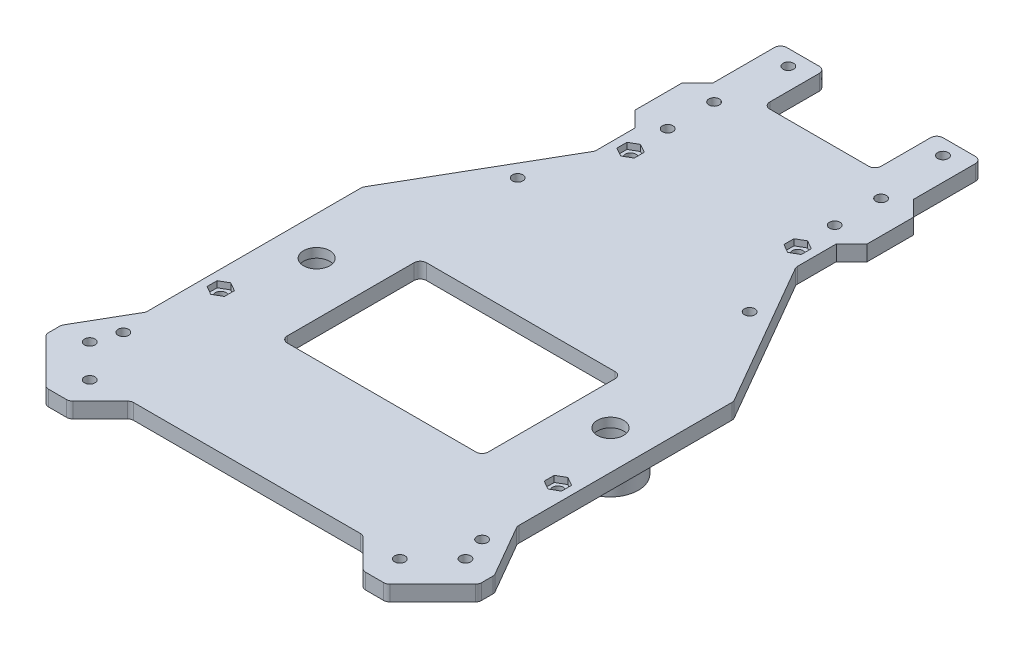
SolidWorks part; units mm, degrees
material "ABS PC"
ref_plane "Front Plane" through (0, 0, 0) normal (0, 0, 1) x (1, 0, 0)
ref_plane "Top Plane" through (0, 0, 0) normal (0, 1, 0) x (1, 0, 0)
ref_plane "Right Plane" through (0, 0, 0) normal (1, 0, 0) x (0, 0, -1)
sketch "Sketch1" plane through (0, 0, 0) normal (0, 1, 0) x (1, 0, 0)
  line L1 (70, -110) -> (-70, -110)
  line L2 (70, -110) -> (70, 110)
  line L3 (70, 110) -> (-70, 110)
  line L4 (-70, -110) -> (-70, 110)
  line L5 (70, -110) -> (-70, 110) construction
  line L6 (70, 110) -> (-70, -110) construction
  point P0 (0, 0)
  dimension "D1" = 220
  dimension "D2" = 140
extrude "Boss-Extrude1" add sketch "Sketch1" along normal blind 5
sketch "Sketch2" plane through (0, 5, 0) normal (0, 1, 0) x (1, 0, 0)
  line L0 (0, 110) -> (0, -110) construction
  line L1 (70, 110) -> (-70, 110) construction
  line L2 (-70, -110) -> (70, -110) construction
  line L4 (15.25, 80.25) -> (-15.25, 80.25) construction
  line L5 (15.25, 80.25) -> (15.25, 49.75) construction
  line L6 (15.25, 49.75) -> (-15.25, 49.75) construction
  line L7 (-15.25, 80.25) -> (-15.25, 49.75) construction
  line L8 (15.25, 80.25) -> (-15.25, 49.75) construction
  line L9 (15.25, 49.75) -> (-15.25, 80.25) construction
  point P6 (0, 65)
  dimension "D1" = 30.5
  dimension "D2" = 45
sketch "Sketch5" plane through (0, 5, 0) normal (0, 1, 0) x (1, 0, 0)
  line L0 (0, 110) -> (0, -110) construction
  line L1 (70, 110) -> (-70, 110) construction
  line L2 (-70, -110) -> (70, -110) construction
  line L4 (-24.5, -34) -> (24.5, -34) construction
  line L5 (-24.5, -34) -> (-24.5, 24) construction
  line L6 (-24.5, 24) -> (24.5, 24) construction
  line L7 (24.5, -34) -> (24.5, 24) construction
  line L8 (-24.5, -34) -> (24.5, 24) construction
  line L9 (-24.5, 24) -> (24.5, -34) construction
  point P6 (0, -5)
  dimension "D1" = 58
  dimension "D2" = 49
  dimension "D3" = 115
sketch "Sketch8" plane through (0, 5, 0) normal (0, 1, 0) x (1, 0, 0)
  line L0 (-70, 110) -> (-32.5, 110)
  line L1 (70, 110) -> (-70, 110) construction
  line L2 (-32.5, 110) -> (-32.5, 44.9519)
  line L3 (-32.5, 44.9519) -> (-70, -20)
  line L4 (-70, 110) -> (-70, -110) construction
  line L5 (-70, 110) -> (-70, -20)
  line L6 (0, 110) -> (0, -110) construction
  line L7 (-70, -110) -> (70, -110) construction
  line L8 (70, 110) -> (70, -20)
  line L9 (32.5, 44.9519) -> (70, -20)
  line L10 (32.5, 110) -> (32.5, 44.9519)
  line L11 (70, 110) -> (32.5, 110)
  dimension "D1" = 130
  dimension "D2" = 30
  dimension "D3" = 65
extrude "Cut-Extrude1" cut sketch "Sketch8" against normal blind 5
chamfer "Chamfer3" distance 15 angle 45 2 edges at (70, 2.5, 110) (-70, 2.5, 110)
sketch "Sketch10" plane through (0, 0, 0) normal (0, 1, 0) x (1, 0, 0)
  line L0 (0, 110) -> (0, -110) construction
  line L1 (32.5, 110) -> (-32.5, 110) construction
  line L2 (-55, -110) -> (55, -110) construction
  line L3 (-27, 78) -> (-27, 63) construction
  line L4 (-62.5, -102.5) -> (-55.4289, -95.4289) construction
  line L5 (-60.7322, -90.1256) -> (-50.1256, -100.7322) construction
  line L6 (-70, -95) -> (-55, -110) construction
  point P9 (27, 63)
  point P10 (27, 78)
  point P17 (50.1256, -100.7322)
  point P18 (60.7322, -90.1256)
  dimension "D1" = 15
  dimension "D2" = 27
  dimension "D3" = 32
  dimension "D4" = 15
  dimension "D5" = 10
sketch "Sketch15" plane through (0, 5, 0) normal (0, 1, 0) x (1, 0, 0)
  line L0 (0, 110) -> (0, -110) construction
  line L1 (32.5, 110) -> (-32.5, 110) construction
  line L2 (-55, -110) -> (55, -110) construction
  line L3 (25, 100) -> (-25, 100) construction
  line L4 (37.5, 25) -> (-37.5, 25) construction
  line L5 (58, -57) -> (-58, -57) construction
  point P9 (0, 100)
  point P13 (0, 25)
  point P15 (0, -57)
  dimension "D1" = 50
  dimension "D2" = 10
  dimension "D3" = 75
  dimension "D4" = 85
  dimension "D5" = 116
  dimension "D6" = 167
hole_wizard "CSK for M3 Flat Head Machine Screw3" positions "Sketch16" profile "Sketch17" countersink size "M3" standard "ANSI Metric"
sketch "Sketch16" plane through (0, 0, 0) normal (0, 1, 0) x (1, 0, 0)
  point P6 (37.5, 25)
  point P9 (-37.5, 25)
  point P12 (-25, 100)
  point P15 (25, 100)
sketch "Sketch17" plane through (37.5, 0, -25) normal (1, 0, 0) x (0, 0, -1)
  line L0 (0, 0) -> (0, 6.0215)
  line L1 (0, 6.0215) -> (1.7, 5)
  line L2 (1.7, 5) -> (1.7, 1.45)
  line L3 (1.7, 1.45) -> (3.15, 0)
  line L5 (3.15, 0) -> (0, 0)
  line L6 (-1.7, 1.45) -> (-3.15, 0) construction
  line L10 (0, 6.0215) -> (-1.7, 5) construction
  line L11 (0, -6.35) -> (0, 107.95) construction
  dimension "Hole Dia." = 3.4
  dimension "Hole Depth" = 5
  dimension "Near C'Sink Dia." = 6.3
  dimension "Near C'Sink Angle" = 90
  dimension "Drill Angle" = 118
sketch "Sketch18" plane through (0, 5, 0) normal (0, 1, 0) x (1, 0, 0)
  line L0 (32.5, 110) -> (-32.5, 110) construction
  line L1 (-46.4338, 114.6286) -> (34.8035, 114.6286)
  line L2 (-46.4338, 114.6286) -> (-46.4338, 105)
  line L3 (-46.4338, 105) -> (34.8035, 105)
  line L4 (34.8035, 114.6286) -> (34.8035, 105)
  dimension "D1" = 5
extrude "Cut-Extrude2" cut sketch "Sketch18" against normal blind 5
sketch "Sketch20" [suppressed] plane through (0, 5, 0) normal (0, 1, 0) x (1, 0, 0)
  line L0 (-36.4478, -76.4478) -> (-74.4101, -114.4101) construction
  line L1 (-27, 81.4641) -> (-30, 79.7321)
  line L2 (-30, 79.7321) -> (-30, 76.2679)
  line L3 (-30, 76.2679) -> (-27, 74.5359)
  line L4 (-27, 74.5359) -> (-24, 76.2679)
  line L5 (-24, 76.2679) -> (-24, 79.7321)
  line L6 (-24, 79.7321) -> (-27, 81.4641)
  line L7 (-27, 63) -> (-27, 78) construction
  line L8 (-19.5617, 70.5) -> (-34.4383, 70.5) construction
  line L9 (-24, 61.2679) -> (-27, 59.5359)
  line L10 (-24, 64.7321) -> (-24, 61.2679)
  line L11 (-27, 66.4641) -> (-24, 64.7321)
  line L12 (-30, 64.7321) -> (-27, 66.4641)
  line L13 (-30, 61.2679) -> (-30, 64.7321)
  line L14 (-27, 59.5359) -> (-30, 61.2679)
  line L15 (0, 105) -> (0, -110) construction
  line L16 (-32.5, 105) -> (32.5, 105) construction
  line L17 (-55, -110) -> (55, -110) construction
  line L18 (-70, -95) -> (-55, -110) construction
  line L19 (-57.3862, -89.2291) -> (-59.8357, -86.7796)
  line L20 (-59.8357, -86.7796) -> (-63.1817, -87.6761)
  line L21 (-63.1817, -87.6761) -> (-64.0783, -91.0222)
  line L22 (-64.0783, -91.0222) -> (-61.6288, -93.4717)
  line L23 (-61.6288, -93.4717) -> (-58.2827, -92.5751)
  line L24 (-58.2827, -92.5751) -> (-57.3862, -89.2291)
  line L25 (-60.7322, -90.1256) -> (-50.1256, -100.7322) construction
  line L26 (-52.5751, -98.2827) -> (-49.2291, -97.3862)
  line L27 (-53.4717, -101.6288) -> (-52.5751, -98.2827)
  line L28 (-51.0222, -104.0783) -> (-53.4717, -101.6288)
  line L29 (-47.6761, -103.1817) -> (-51.0222, -104.0783)
  line L30 (-46.7796, -99.8357) -> (-47.6761, -103.1817)
  line L31 (-49.2291, -97.3862) -> (-46.7796, -99.8357)
  line L32 (60.7322, -90.1256) -> (50.1256, -100.7322) construction
  line L33 (36.4478, -76.4478) -> (74.4101, -114.4101) construction
  line L34 (49.2291, -97.3862) -> (46.7796, -99.8357)
  line L35 (46.7796, -99.8357) -> (47.6761, -103.1817)
  line L36 (47.6761, -103.1817) -> (51.0222, -104.0783)
  line L37 (51.0222, -104.0783) -> (53.4717, -101.6288)
  line L38 (53.4717, -101.6288) -> (52.5751, -98.2827)
  line L39 (52.5751, -98.2827) -> (49.2291, -97.3862)
  line L40 (58.2827, -92.5751) -> (57.3862, -89.2291)
  line L41 (61.6288, -93.4717) -> (58.2827, -92.5751)
  line L42 (64.0783, -91.0222) -> (61.6288, -93.4717)
  line L43 (63.1817, -87.6761) -> (64.0783, -91.0222)
  line L44 (59.8357, -86.7796) -> (63.1817, -87.6761)
  line L45 (57.3862, -89.2291) -> (59.8357, -86.7796)
  line L46 (19.5617, 70.5) -> (34.4383, 70.5) construction
  line L47 (27, 63) -> (27, 78) construction
  line L48 (27, 59.5359) -> (30, 61.2679)
  line L49 (30, 61.2679) -> (30, 64.7321)
  line L50 (30, 64.7321) -> (27, 66.4641)
  line L51 (27, 66.4641) -> (24, 64.7321)
  line L52 (24, 64.7321) -> (24, 61.2679)
  line L53 (24, 61.2679) -> (27, 59.5359)
  line L54 (24, 79.7321) -> (27, 81.4641)
  line L55 (24, 76.2679) -> (24, 79.7321)
  line L56 (27, 74.5359) -> (24, 76.2679)
  line L57 (30, 76.2679) -> (27, 74.5359)
  line L58 (30, 79.7321) -> (30, 76.2679)
  line L59 (27, 81.4641) -> (30, 79.7321)
  circle A0 centre (-27, 78) radius 3 construction
  circle A1 centre (-60.7322, -90.1256) radius 3 construction
  circle A2 centre (60.7322, -90.1256) radius 3 construction
  circle A3 centre (27, 78) radius 3 construction
  point P12 (-27, 70.5)
  point P16 (-27, 70.5)
  point P43 (-55.4289, -95.4289)
  point P66 (55.4289, -95.4289)
  point P84 (27, 70.5)
  dimension "D1" = 6
  dimension "D2" = 6
extrude "Cut-Extrude4" [suppressed] cut sketch "Sketch20" against normal blind 2
sketch "Sketch24" plane through (0, 0, 0) normal (0, -1, 0) x (1, 0, 0)
  line L0 (7.5, -85) -> (-7.5, -85) construction
  line L1 (7.5, -88) -> (-7.5, -88)
  line L2 (7.5, -82) -> (-7.5, -82)
  line L3 (-32.5, -105) -> (32.5, -105) construction
  line L4 (0, 0) -> (0, -85) construction
  arc A0 (7.5, -88) -> (7.5, -82) centre (7.5, -85) ccw
  arc A1 (-7.5, -82) -> (-7.5, -88) centre (-7.5, -85) ccw
  point P2 (0, -85)
  dimension "D1" = 6
  dimension "D2" = 15
  dimension "D3" = 20
extrude "Ultrasonic sensor wires hole" [suppressed] cut sketch "Sketch24" against normal through all
sketch "Sketch26" plane through (0, 0, 0) normal (0, -1, 0) x (1, 0, 0)
  line L0 (0, 14.9245) -> (0, -105.8153) construction
  line L1 (-32.5, -105) -> (32.5, -105) construction
  circle A0 centre (12.5, -65) radius 2.5
  circle A1 centre (-12.5, -65) radius 2.5
  dimension "D1" = 25
  dimension "D2" = 5
  dimension "D3" = 40
extrude "Antennas holes" [suppressed] cut sketch "Sketch26" against normal through all
sketch "Sketch27" [suppressed] plane through (0, 0, 0) normal (0, -1, 0) x (1, 0, 0)
  line L0 (-12.5, -65) -> (-20.5, -65) construction
  line L1 (0, -29.7732) -> (0, -95.9679) construction
  line L2 (-19.5, -68.5) -> (-21.5, -68.5)
  line L3 (-19.5, -68.5) -> (-19.5, -61.5)
  line L4 (-19.5, -61.5) -> (-21.5, -61.5)
  line L5 (-21.5, -68.5) -> (-21.5, -61.5)
  line L6 (-19.5, -68.5) -> (-21.5, -61.5) construction
  line L7 (-19.5, -61.5) -> (-21.5, -68.5) construction
  line L8 (21.5, -68.5) -> (21.5, -61.5)
  line L9 (19.5, -61.5) -> (21.5, -61.5)
  line L10 (19.5, -68.5) -> (19.5, -61.5)
  line L11 (19.5, -68.5) -> (21.5, -68.5)
  dimension "D1" = 2
  dimension "D2" = 7
  dimension "D3" = 8
extrude "Antenna zip ties" [suppressed] cut sketch "Sketch27" against normal through all
sketch "Sketch33" [suppressed] plane through (0, 3, 0) normal (0, 1, 0) x (1, 0, 0)
  line L0 (0, -105.908) -> (0, -114.2602) construction
  circle A0 centre (-26, -82) radius 3.25
  circle A1 centre (26, -82) radius 3.25
  dimension "D1" = 6.5
sketch "Sketch34" plane through (0, 5, 0) normal (0, 1, 0) x (1, 0, 0)
  line L0 (-70, -20) -> (-60, -2.6795)
  line L1 (-70, -20) -> (-32.5, 44.9519) construction
  line L2 (-60, -2.6795) -> (-60, -72.6795)
  line L3 (-60, -72.6795) -> (-70, -90)
  line L4 (-70, -20) -> (-70, -95) construction
  line L5 (-70, -90) -> (-70, -20)
  line L6 (0, -90.4055) -> (0, -61.6307) construction
  line L7 (70, -90) -> (70, -20)
  line L8 (60, -72.6795) -> (70, -90)
  line L9 (60, -2.6795) -> (60, -72.6795)
  line L10 (70, -20) -> (60, -2.6795)
  line L11 (-55, -110) -> (55, -110) construction
  dimension "D1" = 120
  dimension "D2" = 20
extrude "Cut-Extrude8" cut sketch "Sketch34" against normal blind 10
chamfer "Chamfer4" [suppressed] distance 20 angle 30
sketch "Sketch35" plane through (0, 5, 0) normal (0, 1, 0) x (1, 0, 0)
  line L1 (-30.5, -58.5) -> (34.5, -58.5)
  line L2 (-30.5, -58.5) -> (-30.5, -13.5)
  line L3 (-30.5, -13.5) -> (34.5, -13.5)
  line L4 (34.5, -58.5) -> (34.5, -13.5)
  line L5 (-30.5, -58.5) -> (34.5, -13.5) construction
  line L6 (-30.5, -13.5) -> (34.5, -58.5) construction
  point P0 (2, -36)
  dimension "D1" = 2
  dimension "D2" = 65
  dimension "D3" = 45
  dimension "D4" = 36
extrude "Cut-Extrude9" cut sketch "Sketch35" against normal through all
fillet "Fillet1" radius 2 4 edges at (-30.5, 2.5, 58.5) (-30.5, 2.5, 13.5) (34.5, 2.5, 13.5) (34.5, 2.5, 58.5)
sketch "Sketch36" plane through (0, 5, 0) normal (0, 1, 0) x (1, 0, 0)
  line L0 (0, -110) -> (0, -100) construction
  line L1 (-55, -110) -> (55, -110) construction
  line L2 (-47.5, -110) -> (-37.5, -100)
  line L3 (-37.5, -100) -> (37.5, -100)
  line L4 (-47.5, -110) -> (47.5, -110)
  line L6 (-70, -95) -> (-55, -110) construction
  line L7 (47.5, -110) -> (37.5, -100)
  dimension "D1" = 10
  dimension "D2" = 95
extrude "Cut-Extrude10" cut sketch "Sketch36" against normal through all
sketch "Sketch38" plane through (0, 0, 0) normal (0, -1, 0) x (1, 0, 0)
  line L0 (0, -105) -> (0, -90) construction
  line L1 (-32.5, -105) -> (32.5, -105) construction
  line L2 (18, -85) -> (-18, -85)
  line L3 (-18, -85) -> (-18, -105)
  line L4 (-18, -105) -> (18, -105)
  line L5 (18, -85) -> (18, -105)
  dimension "D1" = 90
  dimension "D2" = 20
  dimension "D3" = 36
extrude "Cut-Extrude14" cut sketch "Sketch38" against normal through all
fillet "Fillet2" [suppressed] radius 2
sketch "Sketch39" plane through (0, 0, 0) normal (0, -1, 0) x (1, 0, 0)
  line L0 (0, 37.973) -> (0, 15.9654) construction
  circle A0 centre (-47.5, 30) radius 7
  circle A1 centre (47.5, 30) radius 7
  dimension "D1" = 95
  dimension "D2" = 14
  dimension "D3" = 30
extrude "Cut-Extrude15" cut sketch "Sketch39" against normal through all
hole_wizard "CSK for M3 Flat Head Machine Screw2" positions "Sketch40" profile "Sketch41" countersink size "M3" standard "ANSI Metric"
sketch "Sketch40" plane through (0, 0, 0) normal (0, -1, 0) x (-1, 0, 0)
  point P0 (-58, -82)
  point P3 (58, -82)
sketch "Sketch41" plane through (58, 0, 82) normal (1, 0, 0) x (0, 0, -1)
  line L0 (0, 0) -> (0, 11.0215)
  line L1 (0, 11.0215) -> (1.7, 10)
  line L2 (1.7, 10) -> (1.7, 1.45)
  line L3 (1.7, 1.45) -> (3.15, 0)
  line L5 (3.15, 0) -> (0, 0)
  line L6 (-1.7, 1.45) -> (-3.15, 0) construction
  line L10 (0, 11.0215) -> (-1.7, 10) construction
  line L11 (0, -6.35) -> (0, 107.95) construction
  dimension "Hole Dia." = 3.4
  dimension "Hole Depth" = 10
  dimension "Near C'Sink Dia." = 6.3
  dimension "Near C'Sink Angle" = 90
  dimension "Drill Angle" = 118
sketch "Sketch19" plane through (0, 0, 0) normal (0, -1, 0) x (1, 0, 0)
  line L0 (0, -31.0011) -> (0, -83.9715) construction
  circle A0 centre (-25, -100) radius 3.25
  circle A1 centre (25, -100) radius 3.25
  circle A2 centre (-37.5, -25) radius 3.25
  circle A3 centre (-58, 82) radius 3.25
  circle A4 centre (58, 82) radius 3.25
  circle A5 centre (37.5, -25) radius 3.25
  dimension "D1" = 6.5
extrude "Cut-Extrude3" [suppressed] cut sketch "Sketch19" against normal blind 2
sketch "Sketch42" plane through (0, 5, 0) normal (0, 1, 0) x (1, 0, 0)
  line L0 (0, 24.3504) -> (0, -27.8049) construction
  circle A0 centre (-47.5, -30) radius 4.25
  circle A1 centre (-47.5, -30) radius 7
  circle A2 centre (-47.5, -30) radius 7 construction
  circle A3 centre (47.5, -30) radius 7
  circle A4 centre (47.5, -30) radius 4.25
  dimension "D1" = 8.5
extrude "Boss-Extrude2" add sketch "Sketch42" against normal blind 3
sketch "Sketch43" plane through (0, 0, 0) normal (0, -1, 0) x (1, 0, 0)
  line L0 (0, 44.1268) -> (0, 33.9369) construction
  circle A0 centre (-47.5, 30) radius 7
  circle A1 centre (-47.5, 30) radius 7 construction
  circle A3 centre (-47.5, 30) radius 9
  circle A4 centre (47.5, 30) radius 9
  circle A5 centre (47.5, 30) radius 7
  dimension "D1" = 2
extrude "Boss-Extrude3" add sketch "Sketch43" along normal blind 8
hole_wizard "Ø3.5 (3.5) Diameter Hole1" positions "Sketch45" profile "Sketch46" hole size "Ø3.5" standard "ANSI Metric"
sketch "Sketch45" plane through (0, 5, 0) normal (0, 1, 0) x (1, 0, 0)
  line L0 (-32.5, 44.9519) -> (-32.5, 105) construction
  line L1 (-60, -72.6795) -> (-60, -2.6795) construction
  line L2 (-32.5, 105) -> (-18, 105) construction
  point P0 (-54.5, -54)
  point P2 (-27, 51)
  dimension "D1" = 5.5
  dimension "D2" = 5.5
  dimension "D3" = 54
  dimension "D4" = 105
sketch "Sketch46" plane through (-54.5, 5, 54) normal (1, 0, 0) x (0, 0, 1)
  line L0 (0, 0) -> (0, 6.0515)
  line L1 (0, 6.0515) -> (1.75, 5)
  line L2 (1.75, 5) -> (1.75, 0)
  line L5 (1.75, 0) -> (0, 0)
  line L10 (0, 6.0515) -> (-1.75, 5) construction
  line L11 (0, -6.35) -> (0, 107.95) construction
  dimension "Hole Dia." = 3.5
  dimension "Hole Depth" = 5
  dimension "Drill Angle" = 118
mirror "Mirror1" about plane through (0, 0, 0) normal (1, 0, 0) of "Ø3.5 (3.5) Diameter Hole1"
sketch "Sketch47" plane through (0, 5, 0) normal (0, 1, 0) x (1, 0, 0)
  line L0 (0, 13.2168) -> (0, -3.9151) construction
  line L1 (29.8, 49.3834) -> (29.8, 52.6166)
  line L2 (29.8, 52.6166) -> (27, 54.2332)
  line L3 (27, 54.2332) -> (24.2, 52.6166)
  line L4 (24.2, 52.6166) -> (24.2, 49.3834)
  line L5 (24.2, 49.3834) -> (27, 47.7668)
  line L6 (27, 47.7668) -> (29.8, 49.3834)
  line L7 (57.3, -55.6166) -> (57.3, -52.3834)
  line L8 (57.3, -52.3834) -> (54.5, -50.7668)
  line L9 (54.5, -50.7668) -> (51.7, -52.3834)
  line L10 (51.7, -52.3834) -> (51.7, -55.6166)
  line L11 (51.7, -55.6166) -> (54.5, -57.2332)
  line L12 (54.5, -57.2332) -> (57.3, -55.6166)
  line L13 (-54.5, -57.2332) -> (-57.3, -55.6166)
  line L14 (-51.7, -55.6166) -> (-54.5, -57.2332)
  line L15 (-51.7, -52.3834) -> (-51.7, -55.6166)
  line L16 (-54.5, -50.7668) -> (-51.7, -52.3834)
  line L17 (-57.3, -52.3834) -> (-54.5, -50.7668)
  line L18 (-57.3, -55.6166) -> (-57.3, -52.3834)
  line L19 (-27, 47.7668) -> (-29.8, 49.3834)
  line L20 (-24.2, 49.3834) -> (-27, 47.7668)
  line L21 (-24.2, 52.6166) -> (-24.2, 49.3834)
  line L22 (-27, 54.2332) -> (-24.2, 52.6166)
  line L23 (-29.8, 52.6166) -> (-27, 54.2332)
  line L24 (-29.8, 49.3834) -> (-29.8, 52.6166)
  circle A0 centre (27, 51) radius 2.8 construction
  circle A1 centre (54.5, -54) radius 2.8 construction
  circle A2 centre (-54.5, -54) radius 2.8 construction
  circle A3 centre (-27, 51) radius 2.8 construction
  dimension "D1" = 5.6
extrude "Cut-Extrude16" cut sketch "Sketch47" against normal blind 2
hole_wizard "CSK for M3 Flat Head Machine Screw1" positions "Sketch52" profile "Sketch53" countersink size "M3" standard "ANSI Metric"
sketch "Sketch52" plane through (0, 0, 0) normal (0, -1, 0) x (-1, 0, 0)
  point P0 (27, 63)
  point P3 (27, 78)
  point P6 (-27, 78)
  point P9 (-27, 63)
  point P12 (60.7322, -90.1256)
  point P15 (50.1256, -100.7322)
  point P18 (-50.1256, -100.7322)
  point P21 (-60.7322, -90.1256)
sketch "Sketch53" plane through (-27, 0, -63) normal (1, 0, 0) x (0, 0, -1)
  line L0 (0, 0) -> (0, 6.0215)
  line L1 (0, 6.0215) -> (1.7, 5)
  line L2 (1.7, 5) -> (1.7, 1.45)
  line L3 (1.7, 1.45) -> (3.15, 0)
  line L5 (3.15, 0) -> (0, 0)
  line L6 (-1.7, 1.45) -> (-3.15, 0) construction
  line L10 (0, 6.0215) -> (-1.7, 5) construction
  line L11 (0, -6.35) -> (0, 107.95) construction
  dimension "Hole Dia." = 3.4
  dimension "Hole Depth" = 5
  dimension "Near C'Sink Dia." = 6.3
  dimension "Near C'Sink Angle" = 90
  dimension "Drill Angle" = 118
sketch "Sketch48" plane through (0, 5, 0) normal (0, 1, 0) x (1, 0, 0)
  line L0 (27, 78) -> (27, 63) construction
  line L1 (27, 70.5) -> (37.5, 70.5) construction
  line L2 (32.5, 58) -> (32.5, 83)
  line L3 (32.5, 105) -> (32.5, 44.9519) construction
  line L4 (32.5, 83) -> (37.5, 78)
  line L5 (37.5, 78) -> (37.5, 63)
  line L6 (32.5, 58) -> (37.5, 63)
  line L7 (0, 71.0199) -> (0, 60.9015) construction
  line L8 (-32.5, 58) -> (-37.5, 63)
  line L9 (-37.5, 78) -> (-37.5, 63)
  line L10 (-32.5, 83) -> (-37.5, 78)
  line L11 (-32.5, 58) -> (-32.5, 83)
  point P13 (32.5, 70.5)
  point P16 (-32.5, 70.5)
  dimension "D1" = 45
  dimension "D2" = 5
  dimension "D3" = 25
extrude "Boss-Extrude4" add sketch "Sketch48" against normal up to surface (5 mm away) up to face at (-27, 0, -66.15)
fillet "Fillet3" radius 2 22 edges at (-32.5, 2.5, -105) (-32.5, 2.5, -44.9519) (-60, 2.5, 2.6795) (-60, 2.5, 72.6795) (-70, 2.5, 90) (-70, 2.5, 95) (-55, 2.5, 110) (-47.5, 2.5, 110) (-37.5, 2.5, 100) (37.5, 2.5, 100) (47.5, 2.5, 110) (55, 2.5, 110) (70, 2.5, 95) (70, 2.5, 90) (60, 2.5, 72.6795) (60, 2.5, 2.6795) (32.5, 2.5, -44.9519) (18, 2.5, -105) (18, 2.5, -85) (-18, 2.5, -85) (-18, 2.5, -105) (32.5, 2.5, -105)
